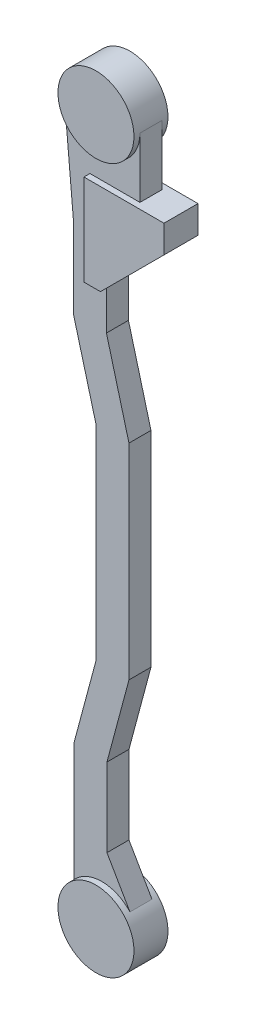
SolidWorks part; units mm, degrees
ref_plane "Front Plane" through (0, 0, 0) normal (0, 0, 1) x (1, 0, 0)
ref_plane "Top Plane" through (0, 0, 0) normal (0, 1, 0) x (1, 0, 0)
ref_plane "Right Plane" through (0, 0, 0) normal (1, 0, 0) x (0, 0, -1)
sketch "Sketch1" plane through (0, 0, 0) normal (0, 0, 1) x (1, 0, 0)
  line L0 (0, 0) -> (0, 705) construction
  line L1 (0, 0) -> (-28, 0) construction
  line L2 (-28, 25.6905) -> (-28, 144)
  line L3 (-28, 144) -> (-6.0004, 226.1037)
  line L4 (-6.0004, 226.1037) -> (-6.0004, 431.1037)
  line L5 (-6.0004, 431.1037) -> (-28.5176, 515.1392)
  line L6 (-28.5176, 515.1392) -> (-28.5176, 596.1392)
  line L7 (-28.5176, 596.1392) -> (-37.8522, 701.6513)
  line L8 (38, 705) -> (38, 645)
  line L9 (38, 645) -> (68, 645)
  line L10 (26.9996, 431.1037) -> (26.9996, 226.1037)
  line L11 (68, 645) -> (-12, 645)
  line L13 (4.4824, 590) -> (0, 590)
  line L14 (-12, 645) -> (-12, 590)
  line L15 (26.9996, 431.1037) -> (4.4824, 515.1392)
  line L16 (26.9996, 226.1037) -> (5, 144)
  line L17 (5, 144) -> (5, 65.5276)
  line L18 (-28, 25.6905) -> (0, 25.6905) construction
  line L19 (28, 25.6905) -> (5, 65.5276)
  line L20 (0, 25.6905) -> (28, 25.6905) construction
  line L21 (-28, 0) -> (-28, 25.6905) construction
  line L22 (4.4824, 515.1392) -> (4.4824, 553.9824)
  line L23 (68, 617.5) -> (4.4824, 553.9824)
  line L24 (68, 590) -> (40.5, 590) construction
  line L25 (68, 617.5) -> (68, 645)
  line L26 (40.5, 590) -> (4.4824, 590) construction
  line L27 (4.4824, 553.9824) -> (4.4824, 590) construction
  line L28 (0, 590) -> (-12, 590) construction
  line L29 (-12, 590) -> (-12, 553.9824)
  line L30 (68, 645) -> (68, 617.5)
  line L31 (4.4824, 553.9824) -> (-12, 553.9824)
  circle A0 centre (0, 0) radius 38
  circle A1 centre (0, 705) radius 38
  dimension "D2" = 76
  dimension "D3" = 28
  dimension "D1" = 705
  dimension "D4" = 144
  dimension "D5" = 165
  dimension "D6" = 85
  dimension "D7" = 205
  dimension "D8" = 165
  dimension "D9" = 87
  dimension "D10" = 81
  dimension "D11" = 60
  dimension "D12" = 30
  dimension "D13" = 55
  dimension "D14" = 80
  dimension "D15" = 33
  dimension "D16" = 205
  dimension "D17" = 150
extrude "Boss-Extrude1" add sketch "Sketch1" along normal blind 11 and the other way blind 11 contours L31 L23 L25 L9 L11 L14 L29 | A1 L7 L6 L5 L4 L3 L2 A0 L19 L17 L16 L10 L15 L22 L31 L29 L14 L11 L8 | A1 | A0 region at (-0.713, 351.4862, 0) region at (0, 0, 0) region at (0, 705, 0) region at (20.7853, 608.8169, 0)
sketch "Sketch3" plane through (0, 0, 0) normal (0, 0, 1) x (1, 0, 0)
  line L0 (68, 617.5) -> (4.4824, 553.9824)
  line L1 (68, 645) -> (-12, 645)
  line L2 (68, 645) -> (68, 617.5)
  line L3 (4.4824, 553.9824) -> (-12, 553.9824)
  line L4 (-12, 645) -> (-12, 553.9824)
  line L5 (68, 553.9824) -> (4.4824, 553.9824) construction
  line L6 (68, 617.5) -> (68, 553.9824) construction
  circle A0 centre (0, 705) radius 38
  circle A1 centre (0, 0) radius 38
  dimension "D1" = 91.0176
  dimension "D2" = 80
extrude "Boss-Extrude2" add sketch "Sketch3" along normal blind 17 and the other way blind 17 contours L1 L4 L3 L0 L2 | A0 | A1
